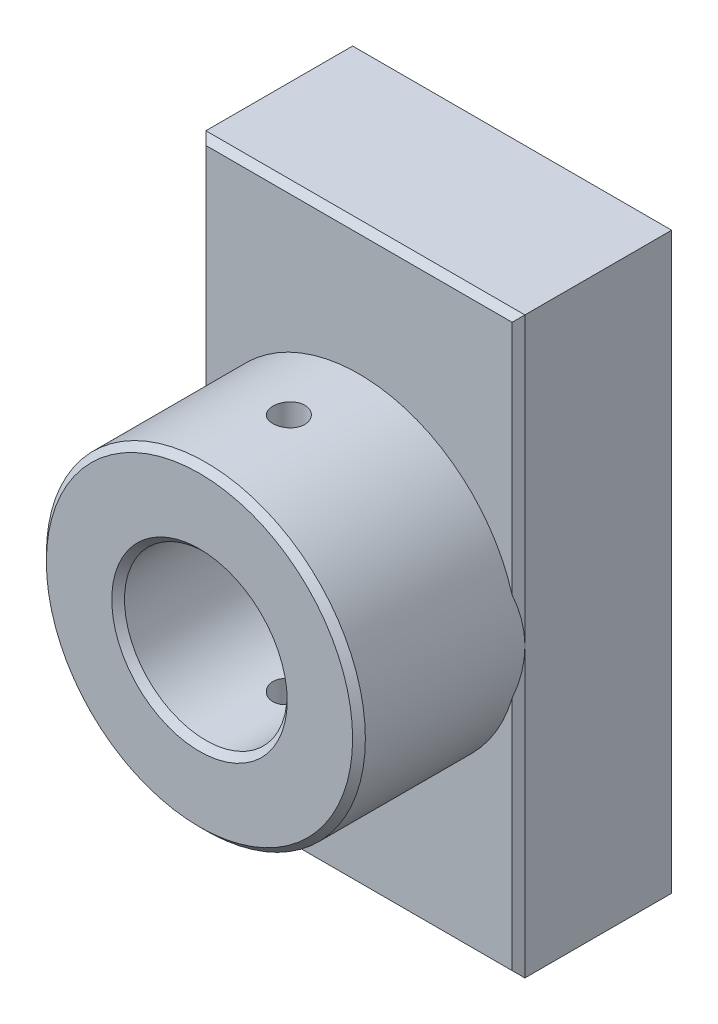
SolidWorks part; units mm, degrees
ref_plane "前视基准面" through (0, 0, 0) normal (0, 0, 1) x (1, 0, 0)
ref_plane "上视基准面" through (0, 0, 0) normal (0, 1, 0) x (1, 0, 0)
ref_plane "右视基准面" through (0, 0, 0) normal (1, 0, 0) x (0, 0, -1)
other "Configuration Table"
sketch "草图1" plane through (0, 0, 0) normal (0, 0, 1) x (1, 0, 0)
  circle A0 centre (0, 0) radius 12.75
  circle A1 centre (0, 0) radius 25
  dimension "D1" = 25.5
  dimension "D2" = 50
extrude "凸台-拉伸1" add sketch "草图1" along normal blind 25
sketch "草图2" plane through (0, 0, 0) normal (0, 1, 0) x (1, 0, 0)
  circle A0 centre (0, -11) radius 2.5
  dimension "D1" = 5
  dimension "D2" = 11
extrude "切除-拉伸1" cut sketch "草图2" against normal blind 30 and the other way blind 30
sketch "草图3" plane through (0, 0, 0) normal (0, 0, -1) x (-1, 0, 0)
  line L1 (-25, 45) -> (25, 45)
  line L2 (-25, 45) -> (-25, -45)
  line L3 (-25, -45) -> (25, -45)
  line L4 (25, 45) -> (25, -45)
  dimension "D1" = 90
  dimension "D2" = 50
  dimension "D3" = 45
  dimension "D4" = 25
extrude "凸台-拉伸2" add sketch "草图3" along normal blind 25
chamfer "倒角1" distance 1 angle 45 2 edges at (25, 0, 25) (12.75, 0, 25)
sketch "草图4" plane through (0, 0, -25) normal (0, 0, -1) x (-1, 0, 0)
  circle A0 centre (2, 0) radius 2.9
  dimension "D1" = 5.8
  dimension "D2" = 2
extrude "切除-拉伸2" cut sketch "草图4" against normal blind 20
chamfer "倒角2" distance 1 angle 45 11 edges at (0, 45, -25) (-25, 0, -25) (0, -45, -25) (25, 0, -25) (-4.9, 0, -25) (25, 22.5, 0) (25, -22.5, 0) (0, -45, 0) (0, 45, 0) (-25, 22.5, 0) (-25, -22.5, 0)
sketch "草图5" plane through (0, 0, -25) normal (0, 0, -1) x (-1, 0, 0)
  line L0 (25, 45) -> (25, -45) construction
  circle A0 centre (2, 34) radius 2.9
  circle A1 centre (2, -34) radius 2.9
  circle A2 centre (2, 0) radius 2.9 construction
  circle A3 centre (2, 0) radius 3.9 construction
  dimension "D1" = 5.8
  dimension "D2" = 5.8
  dimension "D3" = 34
  dimension "D4" = 34
  dimension "D5" = 23
extrude "切除-拉伸3" cut sketch "草图5" against normal blind 20
chamfer "倒角3" distance 0.5 angle 45 2 edges at (-4.9, -34, -25) (-4.9, 34, -25)
